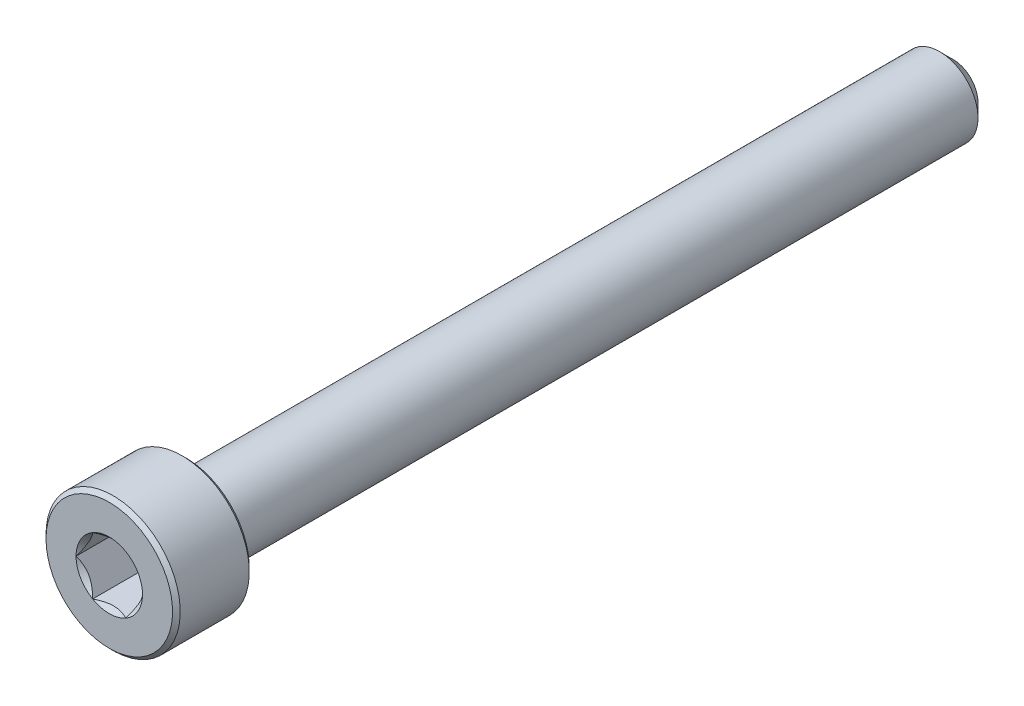
SolidWorks part; units mm, degrees
material "Plain Carbon Steel"
ref_plane "Front Plane" through (0, 0, 0) normal (0, 0, 1) x (1, 0, 0)
ref_plane "Top Plane" through (0, 0, 0) normal (0, 1, 0) x (1, 0, 0)
ref_plane "Right Plane" through (0, 0, 0) normal (1, 0, 0) x (0, 0, -1)
sketch "Sketch1" plane through (0, 0, 0) normal (1, 0, 0) x (0, 0, -1)
  line L0 (-22, 0) -> (22, 0) construction
  line L1 (22, 0) -> (22, 1.3) construction
  line L2 (22, 1.3) -> (21.3, 2) construction
  line L3 (21.3, 2) -> (2, 2) construction
  line L4 (2, 2) -> (-18, 2) construction
  line L5 (-18, 2) -> (-18, 3.5) construction
  line L6 (-18, 3.5) -> (-22, 3.5) construction
  line L7 (-22, 3.5) -> (-22, 0) construction
  line L8 (22, 1.3) -> (22, 2) construction
  line L9 (21.9563, 2.0758) -> (22.3063, 1.4696) construction
  line L10 (22.3063, 1.4696) -> (22.6563, 2.0758) construction
  line L11 (22.6563, 2.0758) -> (21.9563, 2.0758) construction
  line L12 (22.3063, 2.0758) -> (22.3062, 2) construction
  line L13 (22.3063, 1.4696) -> (22.3063, 1.5453) construction
  line L14 (22.2625, 1.5453) -> (22.35, 1.5453) construction
  line L15 (22, 2) -> (22.6125, 2) construction
  line L16 (21.9781, 2.0379) -> (22.6344, 2.0379) construction
  line L17 (22, 0) -> (22, -2) construction
  line L18 (-18.2, 3.5) -> (-18, 3.3) construction
  line L19 (-21.8, 3.5) -> (-22, 3.3) construction
  point P0 (-22, 1.5)
  point P3 (19.55, 2)
  point P4 (0, 0)
  point P18 (1, 2)
  point P22 (22.3063, 1.5453)
  point P24 (2, 2)
  point P25 (22.3062, 2)
  point P28 (22.3063, 2.0379)
  point P29 (19.55, -2)
  point P30 (-17, 2)
  point P31 (-20, 3.5)
  point P37 (-18.7, 3.5)
  point P38 (-21.7, 3.5)
  dimension "head height" = 4
  dimension "threaded length" = 20
  dimension "D1" = 45
  dimension "head dia" = 7
  dimension "thread dia" = 4
  dimension "drive size" = 3
  dimension "pitch" = 0.7
  dimension "D2" = 0.0875
  dimension "D3" = 0.7
  dimension "D4" = 2.45
  dimension "D5" = 1
  dimension "D6" = 1
  dimension "D7" = 0.2
  dimension "D8" = 0.2
  dimension "D9" = 0.2
  dimension "D10" = 0.1
  dimension "D11" = 0.5
  dimension "length" = 40
sketch "Sketch2" plane through (0, 0, 0) normal (1, 0, 0) x (0, 0, -1)
  line L0 (-22, 0) -> (-22, 3.3)
  line L1 (-21.8, 3.5) -> (-18.2, 3.5)
  line L2 (-18, 3.3) -> (-18, 2)
  line L3 (-18, 2) -> (21.3, 2)
  line L4 (21.3, 2) -> (22, 1.3)
  line L5 (22, 1.3) -> (22, 0)
  line L6 (-18.2, 3.5) -> (-18, 3.3) construction
  line L7 (22, 0) -> (-22, 0)
  line L8 (-21.8, 3.5) -> (-22, 3.3) construction
  line L9 (-18.2, 3.5) -> (-18, 3.3)
  line L10 (-21.8, 3.5) -> (-22, 3.3)
revolve "Revolve1" add sketch "Sketch2" angle 360 about L7
sketch "Sketch3" plane through (0, 0, 22) normal (0, 0, 1) x (1, 0, 0)
  line L1 (0.866, 1.5) -> (-0.866, 1.5)
  line L2 (-0.866, 1.5) -> (-1.7321, 0)
  line L3 (-1.7321, 0) -> (-0.866, -1.5)
  line L4 (-0.866, -1.5) -> (0.866, -1.5)
  line L5 (0.866, -1.5) -> (1.7321, 0)
  line L6 (1.7321, 0) -> (0.866, 1.5)
  circle A0 centre (0, 0) radius 1.5 construction
extrude "Cut-Extrude1" cut sketch "Sketch3" against normal offset from surface (3 mm away) 1 up to face at (-3.3, 0, 18)
sketch "Sketch4" plane through (0, 0, 22) normal (0, 0, 1) x (1, 0, 0)
  circle A0 centre (0, 0) radius 1.7321
extrude "Cut-Extrude2" cut sketch "Sketch4" against normal up to vertex (2 mm away) draft 45 up to point (0, 3.5, 20)
ref_plane "Plane1" [suppressed] through (0, 0, -2) normal (0, 0, 1) x (1, 0, 0)
split "Split1" [suppressed] bodies to split 106
sketch "Sketch6" [suppressed] plane through (0, 0, -22) normal (0, 0, -1) x (-1, 0, 0)
  circle A0 centre (0, 0) radius 2
curve "Helix/Spiral1" [suppressed] pitch 0.7 height 20.7 turns 29.5714
sketch "Sketch7" [suppressed] plane through (0, 0, 0) normal (1, 0, 0) x (0, 0, -1)
  line L0 (21.9781, 2.0379) -> (22.6344, 2.0379)
  line L1 (22.6344, 2.0379) -> (22.35, 1.5453)
  line L2 (22.35, 1.5453) -> (22.2625, 1.5453)
  line L3 (22.2625, 1.5453) -> (21.9781, 2.0379)
sweep "Cut-Sweep1" [suppressed] cut profiles "Sketch7" path "Helix/Spiral1"
sketch "Sketch8" [suppressed] plane through (0, 0, -2) normal (0, 0, -1) x (-1, 0, 0)
  circle A0 centre (0, 0) radius 2
extrude "Boss-Extrude1" [suppressed] add sketch "Sketch8" along normal through all draft 45
ref_plane "Plane2" [suppressed] through (0, 0, 20) normal (0, 0, 1) x (1, 0, 0)
sketch "Sketch9" [suppressed] plane through (0, 0, 20) normal (0, 0, 1) x (1, 0, 0)
  line L0 (0, 3.325) -> (0.0611, 3.4995)
  line L1 (0, 3.325) -> (-0.0611, 3.4995)
  line L2 (0, 3.5) -> (0, 0) construction
  line L3 (-0.0611, 3.4995) -> (0, 0) construction
  line L4 (0, 0) -> (0.0611, 3.4995) construction
  arc A0 (0.0611, 3.4995) -> (-0.0611, 3.4995) centre (0, 0) ccw
  circle A1 centre (0, 0) radius 3.325 construction
  dimension "D2" = 6.65
  dimension "D3" = 2
extrude "Cut-Extrude4" [suppressed] cut sketch "Sketch9" against normal up to vertex and the other way up to vertex
pattern_circular "CirPattern2" [suppressed] count 175 over 360 about axis through (0, 0, 22) along (0, 0, -1) of bodies 113
equation "\"D2@Sketch1\"=\"pitch@Sketch1\"/8"
equation "\"D3@Sketch1\"=\"pitch@Sketch1\""
equation "\"D3@Helix/Spiral1\"=\"threaded length@Sketch1\"+\"pitch@Sketch1\""
equation "\"D4@Helix/Spiral1\"=\"pitch@Sketch1\""
equation "\"D4@Sketch1\"=\"pitch@Sketch1\"*3.5"
equation "\"D7@Sketch1\"=\"head height@Sketch1\"*.05"
equation "\"D8@Sketch1\"=\"D7@Sketch1\""
equation "\"D9@Sketch1\"=\"D7@Sketch1\""
equation "\"D10@Sketch1\"=\"D7@Sketch1\"/2"
equation "\"D11@Sketch1\"=\"D10@Sketch1\"*5"
equation "\"D2@Sketch9\"=\"D1@Sketch9\"*.95"
equation "\"D1@CirPattern2\"= ( 360 / \"D3@Sketch9\" ) - 5"
